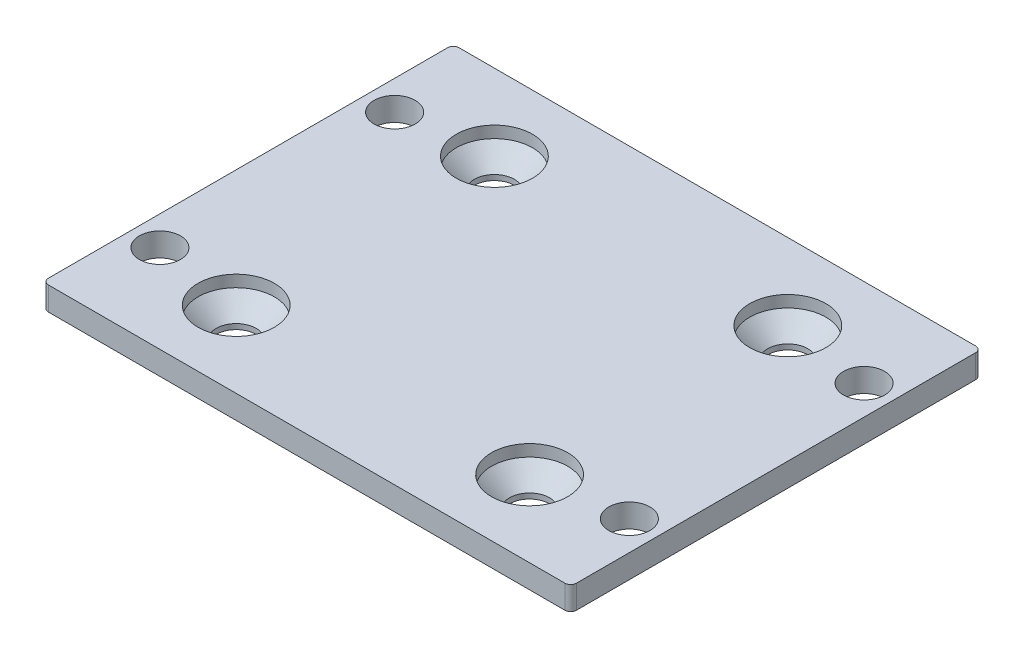
SolidWorks part; units mm, degrees
ref_plane "Plan de face" through (0, 0, 0) normal (0, 0, 1) x (1, 0, 0)
ref_plane "Plan de dessus" through (0, 0, 0) normal (0, 1, 0) x (1, 0, 0)
ref_plane "Plan de droite" through (0, 0, 0) normal (1, 0, 0) x (0, 0, -1)
sketch "Esquisse1" plane through (0, 0, 0) normal (0, 1, 0) x (1, 0, 0)
  line L1 (-22.5, 17.5) -> (22.5, 17.5)
  line L2 (-22.5, 17.5) -> (-22.5, -17.5)
  line L3 (-22.5, -17.5) -> (22.5, -17.5)
  line L4 (22.5, 17.5) -> (22.5, -17.5)
  line L5 (-22.5, 17.5) -> (22.5, -17.5) construction
  line L6 (-22.5, -17.5) -> (22.5, 17.5) construction
  point P0 (0, 0)
  dimension "D1" = 35
  dimension "D2" = 45
extrude "Boss.-Extru.1" add sketch "Esquisse1" along normal blind 2
sketch "Esquisse2" plane through (0, 0, 0) normal (0, -1, 0) x (1, 0, 0)
  line L1 (-17.5, 16) -> (17.5, 16)
  line L2 (-17.5, 16) -> (-17.5, -16)
  line L3 (-17.5, -16) -> (17.5, -16)
  line L4 (17.5, 16) -> (17.5, -16)
  line L5 (-17.5, 16) -> (17.5, -16) construction
  line L6 (-17.5, -16) -> (17.5, 16) construction
  point P0 (0, 0)
  dimension "D1" = 32
  dimension "D2" = 35
extrude "Boss.-Extru.2" add sketch "Esquisse2" along normal blind 1
fillet "Congé1" radius 5 4 edges at (17.5, -0.5, 16) (-17.5, -0.5, -16) (17.5, -0.5, -16) (-17.5, -0.5, 16)
fillet "Congé2" radius 0.5 4 edges at (22.5, 1, -17.5) (-22.5, 1, -17.5) (22.5, 1, 17.5) (-22.5, 1, 17.5)
chamfer "Chanfrein1" distance 0.5 angle 45 8 edges at (17.5, -1, 0) (16.0355, -1, 14.5355) (16.0355, -1, -14.5355) (0, -1, 16) (0, -1, -16) (-16.0355, -1, 14.5355) (-16.0355, -1, -14.5355) (-17.5, -1, 0)
sketch "Esquisse3" plane through (0, 0, 0) normal (0, -1, 0) x (1, 0, 0)
  line L1 (20, -10) -> (-20, -10) construction
  line L2 (20, -10) -> (20, 10) construction
  line L3 (20, 10) -> (-20, 10) construction
  line L4 (-20, -10) -> (-20, 10) construction
  line L5 (20, -10) -> (-20, 10) construction
  line L6 (20, 10) -> (-20, -10) construction
  circle A0 centre (-20, 10) radius 1.75
  circle A1 centre (20, 10) radius 1.75
  circle A2 centre (20, -10) radius 1.75
  circle A3 centre (-20, -10) radius 1.75
  point P0 (0, 0)
  dimension "D3" = 3.5
  dimension "D1" = 40
  dimension "D2" = 20
extrude "Enlèv. mat.-Extru.1" cut sketch "Esquisse3" against normal through all
hole_wizard "Diamètre du perçage Ø6.5 (6.5)1" positions "Esquisse8" profile "Esquisse9" hole size "Ø6.5" standard "ISO"
sketch "Esquisse8" plane through (0, 2, 0) normal (0, 1, 0) x (1, 0, 0)
  line L1 (-12.5, -11) -> (12.5, -11)
  line L2 (-12.5, -11) -> (-12.5, 11)
  line L3 (-12.5, 11) -> (12.5, 11)
  line L4 (12.5, -11) -> (12.5, 11)
  line L5 (-12.5, 0) -> (0, 0)
  line L6 (0, 0) -> (0, 11)
  point P0 (-12.5, -11)
  point P1 (12.5, 11)
  point P8 (-12.5, 11)
  point P9 (12.5, -11)
  dimension "D1" = 22
  dimension "D2" = 25
sketch "Esquisse9" plane through (-12.5, 2, 11) normal (1, 0, 0) x (0, 0, 1)
  line L0 (0, 0) -> (0, 1)
  line L1 (0, 1) -> (3.25, 1)
  line L2 (3.25, 1) -> (3.25, 0)
  line L5 (3.25, 0) -> (0, 0)
  line L10 (0, 1) -> (-3.25, 1) construction
  line L11 (0, -6.35) -> (0, 107.95) construction
  dimension "Diamètre du perçage" = 6.5
  dimension "Profondeur du perçage" = 1
  dimension "Angle de pointe" = 180
hole_wizard "Fraisage pour vis à tête fraisée à 6 pans creux M31" positions "Esquisse5" profile "Esquisse4" countersink size "M3" standard "DIN" end condition through all
sketch "Esquisse5" plane through (0, 1, 0) normal (0, 1, 0) x (1, 0, 0)
  line L1 (-12.5, 11) -> (12.5, 11)
  line L2 (-12.5, 11) -> (-12.5, -11)
  line L3 (-12.5, -11) -> (12.5, -11)
  line L4 (12.5, 11) -> (12.5, -11)
  line L5 (-12.5, 0) -> (0, 0)
  line L6 (0, 0) -> (0, 11)
  point P1 (-12.5, 11)
  point P2 (12.5, -11)
  point P81 (-12.5, -11)
  point P82 (12.5, 11)
  dimension "D1" = 25
  dimension "D2" = 22
sketch "Esquisse4" plane through (-12.5, 1, -11) normal (1, 0, 0) x (0, 0, 1)
  line L0 (0, 0) -> (0, 2)
  line L1 (0, 2) -> (1.7, 2)
  line L2 (1.7, 2) -> (1.7, 1.55)
  line L3 (1.7, 1.55) -> (3.25, 0)
  line L5 (3.25, 0) -> (0, 0)
  line L6 (-1.7, 1.55) -> (-3.25, 0) construction
  line L11 (0, -6.35) -> (0, 107.95) construction
  dimension "Diamètre du perçage jusqu'au prochain" = 3.4
  dimension "Profondeur du perçage jusqu'au prochain" = 2
  dimension "Diamètre du fraisage entrant" = 6.5
  dimension "Angle du fraisage entrant" = 90
